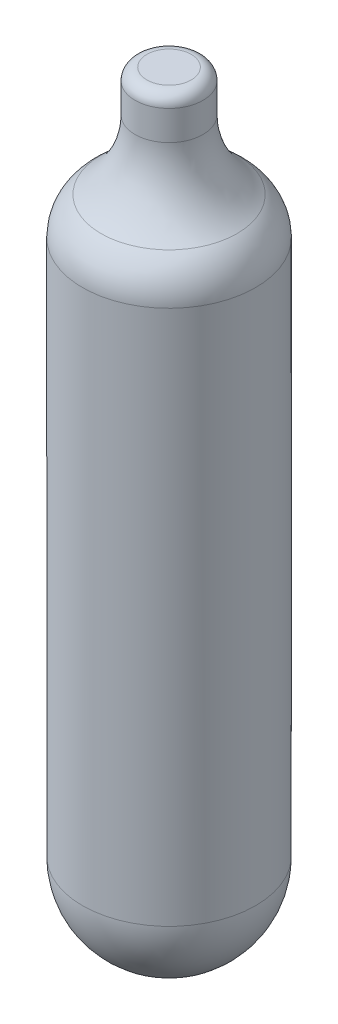
SolidWorks part; units mm, degrees
ref_plane "Front Plane" through (0, 0, 0) normal (0, 0, 1) x (1, 0, 0)
ref_plane "Top Plane" through (0, 0, 0) normal (0, 1, 0) x (1, 0, 0)
ref_plane "Right Plane" through (0, 0, 0) normal (1, 0, 0) x (0, 0, -1)
sketch "Sketch2" plane through (0, 0, 0) normal (0, 1, 0) x (1, 0, 0)
  circle A0 centre (0, 0) radius 9.3218
extrude "Boss-Extrude1" add sketch "Sketch2" along normal blind 82.8802
fillet "Fillet1" radius 9.3218 1 edges at (0, 0, 9.3218)
sketch "Sketch3" plane through (0, 82.8802, 0) normal (0, 1, 0) x (1, 0, 0)
  circle A0 centre (0, 0) radius 3.6576
  circle A1 centre (0, 0) radius 9.3218
extrude "Cut-Extrude1" cut sketch "Sketch3" against normal blind 13.0302
fillet "Fillet2" radius 9.3218 1 edges at (0, 69.85, 3.6576)
fillet "Fillet3" radius 5.08 1 edges at (0, 69.85, 9.3218)
fillet "Fillet5" radius 1.27 1 edges at (0, 82.8802, 3.6576)
ref_axis "Axis1" through (0, -4.144, 0) along (0, 1, 0)
